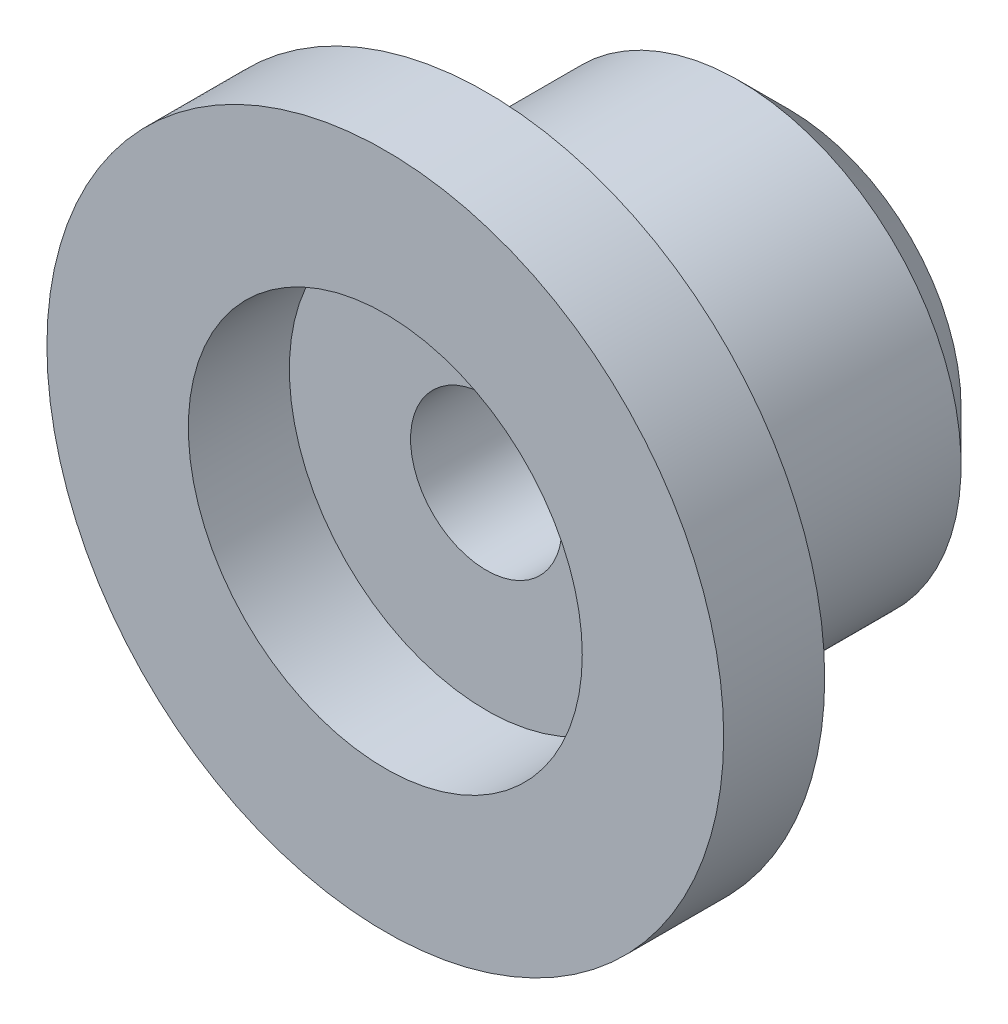
SolidWorks part; units mm, degrees
ref_plane "Front Plane" through (0, 0, 0) normal (0, 0, 1) x (1, 0, 0)
ref_plane "Top Plane" through (0, 0, 0) normal (0, 1, 0) x (1, 0, 0)
ref_plane "Right Plane" through (0, 0, 0) normal (1, 0, 0) x (0, 0, -1)
sketch "Sketch1" plane through (0, 0, 0) normal (0, 0, 1) x (1, 0, 0)
  line L6 (-129.2422, -2.034) -> (-131.9806, -2.034)
  line L7 (-131.9806, -2.034) -> (-131.9806, -4.066)
  line L8 (-131.9806, -4.066) -> (-129.2422, -4.066)
  line L9 (-129.2422, -2.034) -> (-131.9806, -2.034)
  line L10 (-131.9806, -2.034) -> (-131.9806, -4.066)
  line L11 (-131.9806, -4.066) -> (-129.2422, -4.066)
  arc A2 (-129.2422, -4.066) -> (-129.2422, -2.034) centre (-126.05, -3.05) ccw
  arc A3 (-129.2422, -4.066) -> (-129.2422, -2.034) centre (-126.05, -3.05) ccw
  dimension "D1" = 0.15
extrude "Boss-Extrude1" add sketch "Sketch1" against normal up to surface (1 mm away)
sketch "Sketch2" plane through (0, 0, -1) normal (0, 0, -1) x (-1, 0, 0)
  circle A0 centre (126.05, -3.05) radius 2.2
  circle A1 centre (126.05, -3.05) radius 2.5 construction
  dimension "D1" = 0.3
extrude "Boss-Extrude2" add sketch "Sketch2" along normal blind 3
chamfer "Chamfer1" distance 0.5 angle 45 1 edges at (-128.25, -3.05, -4)
sketch "Sketch4" plane through (0, 0, 0) normal (0, 0, 1) x (1, 0, 0)
  circle A0 centre (-126.05, -3.05) radius 1.95
  dimension "D1" = 3.9
extrude "Cut-Extrude1" cut sketch "Sketch4" against normal blind 1
sketch "Sketch5" plane through (0, 0, -1) normal (0, 0, 1) x (1, 0, 0)
  circle A0 centre (-126.05, -3.05) radius 0.75
  dimension "D1" = 1.5
extrude "Cut-Extrude2" cut sketch "Sketch5" against normal offset from surface (2.5 mm away) 0.5 up to face at (-127.75, -3.05, -4)
sketch "Sketch6" plane through (0, 0, -1) normal (0, 0, -1) x (-1, 0, 0)
  circle A0 centre (126.05, -3.05) radius 3.35
  circle A1 centre (126.05, -3.05) radius 6.3753
extrude "Cut-Extrude3" cut sketch "Sketch6" against normal through all
